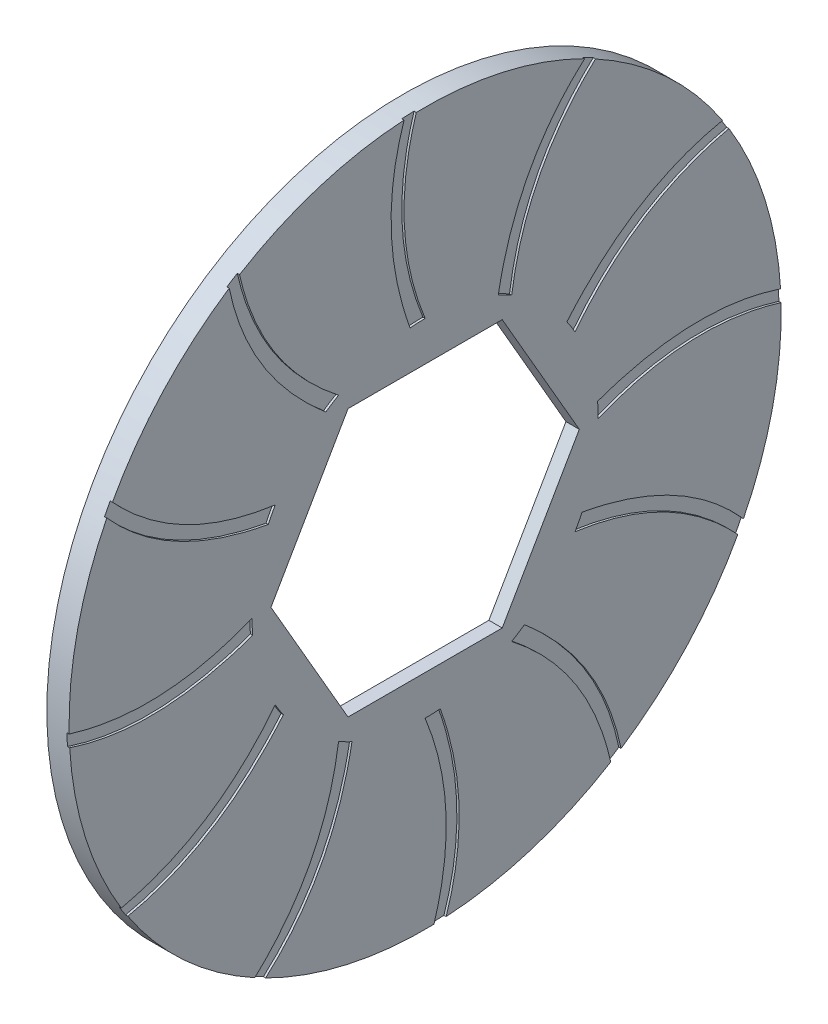
SolidWorks part; units mm, degrees
material "6061 Alloy"
ref_plane "Front Plane" through (0, 0, 0) normal (0, 0, 1) x (1, 0, 0)
ref_plane "Top Plane" through (0, 0, 0) normal (0, 1, 0) x (1, 0, 0)
ref_plane "Right Plane" through (0, 0, 0) normal (1, 0, 0) x (0, 0, -1)
sketch "Sketch1" plane through (0, 0, 0) normal (1, 0, 0) x (0, 0, -1)
  line L1 (6.9282, 0) -> (3.4641, 6)
  line L2 (3.4641, 6) -> (-3.4641, 6)
  line L3 (-3.4641, 6) -> (-6.9282, 0)
  line L4 (-6.9282, 0) -> (-3.4641, -6)
  line L5 (-3.4641, -6) -> (3.4641, -6)
  line L6 (3.4641, -6) -> (6.9282, 0)
  circle A0 centre (0, 0) radius 16
  circle A1 centre (0, 0) radius 6 construction
  circle A2 centre (0, 0) radius 8.5
  dimension "D2" = 32
  dimension "D3" = 17
  dimension "D1" = 12
extrude "Boss-Extrude1" add sketch "Sketch1" along normal blind 1 contours A0 A2 | A2 L6 L5 L4 L3 L2 L1 region at (0, 0, 15.5475) region at (0, 0, 8.2596)
extrude "Cut-Extrude1" cut sketch "Sketch1<3>" along normal blind 0.4 contours A2 L6 L5 L4 L3 L2 L1 region at (0, 0, 8.2596)
sketch "Sketch1<3>" plane through (0, 0, 0) normal (1, 0, 0) x (0, 0, -1) same geometry as "Sketch1"
sketch "Sketch2" plane through (1, 0, 0) normal (1, 0, 0) x (0, 0, -1)
  circle A0 centre (0, 0) radius 7.7783 construction
  circle A1 centre (0, 0) radius 16.1782 construction
  arc A2 (0, 7.7783) -> (-0.6779, 7.7487) centre (0, 0) ccw
  arc A3 (-0.3391, 16.1747) -> (-0.8831, 16.1541) centre (0, 0) ccw
  arc A4 (3.8892, 6.7362) -> (3.2873, 7.0495) centre (0, 0) ccw
  arc A5 (7.7937, 14.1772) -> (7.3123, 14.4314) centre (0, 0) ccw
  arc A6 (6.7362, 3.8892) -> (6.3716, 4.4615) centre (0, 0) ccw
  arc A7 (13.8381, 8.381) -> (13.5483, 8.8418) centre (0, 0) ccw
  arc A8 (7.7783, 0) -> (7.7487, 0.6779) centre (0, 0) ccw
  arc A9 (16.1747, 0.3391) -> (16.1541, 0.8831) centre (0, 0) ccw
  arc A10 (6.7362, -3.8892) -> (7.0495, -3.2873) centre (0, 0) ccw
  arc A11 (14.1772, -7.7937) -> (14.4314, -7.3123) centre (0, 0) ccw
  arc A12 (3.8892, -6.7362) -> (4.4615, -6.3716) centre (0, 0) ccw
  arc A13 (8.381, -13.8381) -> (8.8418, -13.5483) centre (0, 0) ccw
  arc A14 (0, -7.7783) -> (0.6779, -7.7487) centre (0, 0) ccw
  arc A15 (0.3391, -16.1747) -> (0.8831, -16.1541) centre (0, 0) ccw
  arc A16 (-3.8892, -6.7362) -> (-3.2873, -7.0495) centre (0, 0) ccw
  arc A17 (-7.7937, -14.1772) -> (-7.3123, -14.4314) centre (0, 0) ccw
  arc A18 (-6.7362, -3.8892) -> (-6.3716, -4.4615) centre (0, 0) ccw
  arc A19 (-13.8381, -8.381) -> (-13.5483, -8.8418) centre (0, 0) ccw
  arc A20 (-7.7783, 0) -> (-7.7487, -0.6779) centre (0, 0) ccw
  arc A21 (-16.1747, -0.3391) -> (-16.1541, -0.8831) centre (0, 0) ccw
  arc A22 (-6.7362, 3.8892) -> (-7.0495, 3.2873) centre (0, 0) ccw
  arc A23 (-14.1772, 7.7937) -> (-14.4314, 7.3123) centre (0, 0) ccw
  arc A24 (-3.8892, 6.7362) -> (-4.4615, 6.3716) centre (0, 0) ccw
  arc A25 (-8.381, 13.8381) -> (-8.8418, 13.5483) centre (0, 0) ccw
  spline S0 degree 2 poles (0, 7.7783) (-1.7087, 11.9934) (-0.3391, 16.1747) knots 0 0 0 1 1 1
  spline S1 degree 2 poles (-0.8831, 16.1541) (-2.2721, 12.1821) (-0.6779, 7.7487) knots 0 0 0 1 1 1
  spline S2 degree 2 poles (3.8892, 6.7362) (4.5169, 11.241) (7.7937, 14.1772) knots 0 0 0 1 1 1
  spline S3 degree 2 poles (7.3123, 14.4314) (4.1234, 11.6861) (3.2873, 7.0495) knots 0 0 0 1 1 1
  spline S4 degree 2 poles (6.7362, 3.8892) (9.5323, 7.4765) (13.8381, 8.381) knots 0 0 0 1 1 1
  spline S5 degree 2 poles (13.5483, 8.8418) (9.414, 8.0588) (6.3716, 4.4615) knots 0 0 0 1 1 1
  spline S6 degree 2 poles (7.7783, 0) (11.9934, 1.7087) (16.1747, 0.3391) knots 0 0 0 1 1 1
  spline S7 degree 2 poles (16.1541, 0.8831) (12.1821, 2.2721) (7.7487, 0.6779) knots 0 0 0 1 1 1
  spline S8 degree 2 poles (6.7362, -3.8892) (11.241, -4.5169) (14.1772, -7.7937) knots 0 0 0 1 1 1
  spline S9 degree 2 poles (14.4314, -7.3123) (11.6861, -4.1234) (7.0495, -3.2873) knots 0 0 0 1 1 1
  spline S10 degree 2 poles (3.8892, -6.7362) (7.4765, -9.5323) (8.381, -13.8381) knots 0 0 0 1 1 1
  spline S11 degree 2 poles (8.8418, -13.5483) (8.0588, -9.414) (4.4615, -6.3716) knots 0 0 0 1 1 1
  spline S12 degree 2 poles (0, -7.7783) (1.7087, -11.9934) (0.3391, -16.1747) knots 0 0 0 1 1 1
  spline S13 degree 2 poles (0.8831, -16.1541) (2.2721, -12.1821) (0.6779, -7.7487) knots 0 0 0 1 1 1
  spline S14 degree 2 poles (-3.8892, -6.7362) (-4.5169, -11.241) (-7.7937, -14.1772) knots 0 0 0 1 1 1
  spline S15 degree 2 poles (-7.3123, -14.4314) (-4.1234, -11.6861) (-3.2873, -7.0495) knots 0 0 0 1 1 1
  spline S16 degree 2 poles (-6.7362, -3.8892) (-9.5323, -7.4765) (-13.8381, -8.381) knots 0 0 0 1 1 1
  spline S17 degree 2 poles (-13.5483, -8.8418) (-9.414, -8.0588) (-6.3716, -4.4615) knots 0 0 0 1 1 1
  spline S18 degree 2 poles (-7.7783, 0) (-11.9934, -1.7087) (-16.1747, -0.3391) knots 0 0 0 1 1 1
  spline S19 degree 2 poles (-16.1541, -0.8831) (-12.1821, -2.2721) (-7.7487, -0.6779) knots 0 0 0 1 1 1
  spline S20 degree 2 poles (-6.7362, 3.8892) (-11.241, 4.5169) (-14.1772, 7.7937) knots 0 0 0 1 1 1
  spline S21 degree 2 poles (-14.4314, 7.3123) (-11.6861, 4.1234) (-7.0495, 3.2873) knots 0 0 0 1 1 1
  spline S22 degree 2 poles (-3.8892, 6.7362) (-7.4765, 9.5323) (-8.381, 13.8381) knots 0 0 0 1 1 1
  spline S23 degree 2 poles (-8.8418, 13.5483) (-8.0588, 9.414) (-4.4615, 6.3716) knots 0 0 0 1 1 1
  dimension "D1" = 12
extrude "Cut-Extrude2" cut sketch "Sketch2" against normal blind 0.1
